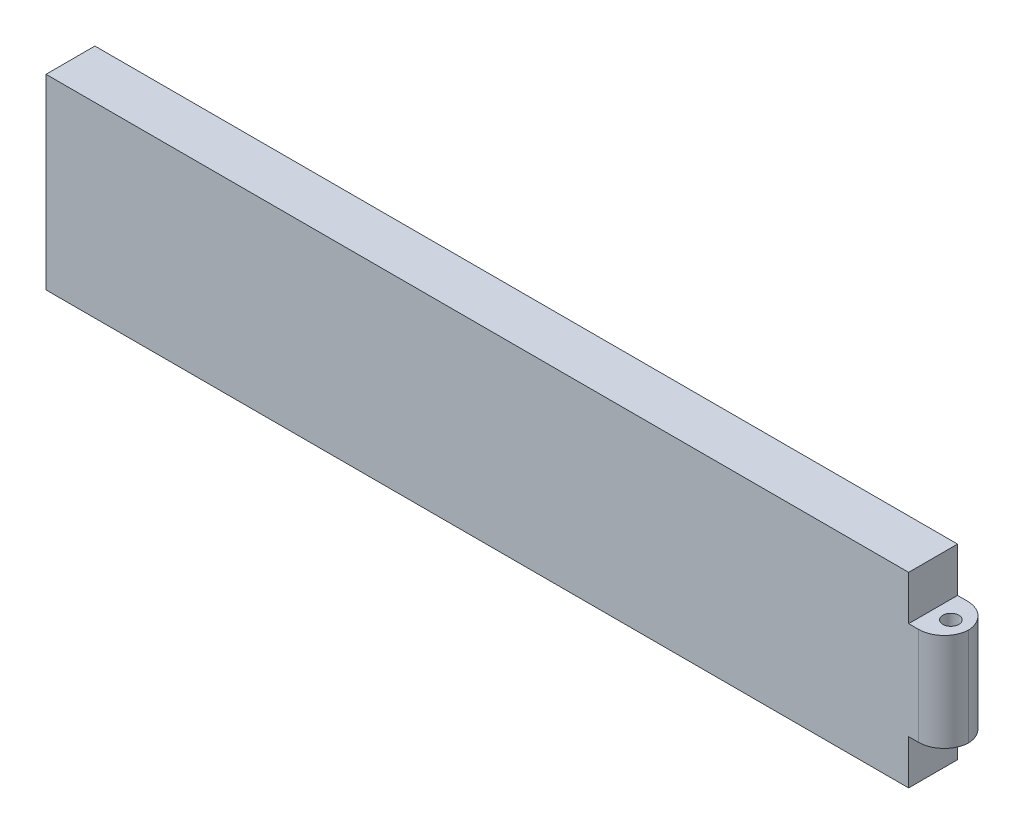
SolidWorks part; units mm, degrees
ref_plane "Front Plane" through (0, 0, 0) normal (0, 0, 1) x (1, 0, 0)
ref_plane "Top Plane" through (0, 0, 0) normal (0, 1, 0) x (1, 0, 0)
ref_plane "Right Plane" through (0, 0, 0) normal (1, 0, 0) x (0, 0, -1)
sketch "Sketch1" plane through (0, 0, 0) normal (0, 1, 0) x (1, 0, 0)
  line L1 (-50.5, -2.75) -> (50.5, -2.75)
  line L2 (-50.5, -2.75) -> (-50.5, 2.75)
  line L3 (-50.5, 2.75) -> (50.5, 2.75)
  line L4 (50.5, -2.75) -> (50.5, 2.75)
  line L5 (-50.5, -2.75) -> (50.5, 2.75) construction
  line L6 (-50.5, 2.75) -> (50.5, -2.75) construction
  point P0 (0, 0)
  dimension "D1" = 101
  dimension "D2" = 5.5
extrude "Boss-Extrude1" add sketch "Sketch1" along normal blind 21
sketch "Sketch2" plane through (0, 0, 0) normal (0, -1, 0) x (1, 0, 0)
  line L0 (-50.5, -2.75) -> (-50.5, 2.75) construction
  line L1 (-49.5, -1.8961) -> (-34.5, -1.8961)
  line L2 (-49.5, -1.8961) -> (-49.5, 1.8961)
  line L3 (-49.5, 1.8961) -> (-34.5, 1.8961)
  line L4 (-34.5, -1.8961) -> (-34.5, 1.8961)
  line L5 (-49.5, -1.8961) -> (-34.5, 1.8961) construction
  line L6 (-49.5, 1.8961) -> (-34.5, -1.8961) construction
  line L7 (-33.5, -1.8961) -> (-18.5, -1.8961)
  line L8 (-33.5, -1.8961) -> (-33.5, 1.8961)
  line L9 (-33.5, 1.8961) -> (-18.5, 1.8961)
  line L10 (-18.5, -1.8961) -> (-18.5, 1.8961)
  line L11 (-33.5, -1.8961) -> (-18.5, 1.8961) construction
  line L12 (-33.5, 1.8961) -> (-18.5, -1.8961) construction
  line L13 (-17.5, -1.8961) -> (-2.5, -1.8961)
  line L14 (-17.5, -1.8961) -> (-17.5, 1.8961)
  line L15 (-17.5, 1.8961) -> (-2.5, 1.8961)
  line L16 (-2.5, -1.8961) -> (-2.5, 1.8961)
  line L17 (-17.5, -1.8961) -> (-2.5, 1.8961) construction
  line L18 (-17.5, 1.8961) -> (-2.5, -1.8961) construction
  line L19 (-1.5, -1.8961) -> (13.5, -1.8961)
  line L20 (-1.5, -1.8961) -> (-1.5, 1.8961)
  line L21 (-1.5, 1.8961) -> (13.5, 1.8961)
  line L22 (13.5, -1.8961) -> (13.5, 1.8961)
  line L23 (-1.5, -1.8961) -> (13.5, 1.8961) construction
  line L24 (-1.5, 1.8961) -> (13.5, -1.8961) construction
  line L25 (14.5, -1.8961) -> (29.5, -1.8961)
  line L26 (14.5, -1.8961) -> (14.5, 1.8961)
  line L27 (14.5, 1.8961) -> (29.5, 1.8961)
  line L28 (29.5, -1.8961) -> (29.5, 1.8961)
  line L29 (14.5, -1.8961) -> (29.5, 1.8961) construction
  line L30 (14.5, 1.8961) -> (29.5, -1.8961) construction
  line L31 (30.5, -1.8961) -> (45.5, -1.8961)
  line L32 (30.5, -1.8961) -> (30.5, 1.8961)
  line L33 (30.5, 1.8961) -> (45.5, 1.8961)
  line L34 (45.5, -1.8961) -> (45.5, 1.8961)
  line L35 (30.5, -1.8961) -> (45.5, 1.8961) construction
  line L36 (30.5, 1.8961) -> (45.5, -1.8961) construction
  line L37 (50.5, 2.75) -> (50.5, -2.75) construction
  circle A0 centre (48.5, 0) radius 0.9
  point P0 (-42, 0)
  point P5 (-26, 0)
  point P10 (-10, 0)
  point P15 (6, 0)
  point P20 (22, 0)
  point P25 (38, 0)
  point P34 (50.5, 0)
  dimension "D13" = 1.8
  dimension "D14" = 2
  dimension "D1" = 1
  dimension "D2" = 15
  dimension "D3" = 1
  dimension "D4" = 1
  dimension "D5" = 1
  dimension "D6" = 1
  dimension "D7" = 1
  dimension "D8" = 15
  dimension "D9" = 15
  dimension "D10" = 15
  dimension "D11" = 15
  dimension "D12" = 15
extrude "Cut-Extrude2" cut sketch "Sketch2" against normal blind 20
sketch "Sketch3" plane through (0, 0, -2.75) normal (0, 0, -1) x (-1, 0, 0)
  line L0 (-50.5, 21) -> (50.5, 21) construction
  line L1 (-46.5, 5) -> (-50.5, 5)
  line L2 (-46.5, 5) -> (-46.5, 0)
  line L3 (-46.5, 0) -> (-50.5, 0)
  line L4 (-50.5, 5) -> (-50.5, 0)
  line L5 (-46.5, 5) -> (-50.5, 0) construction
  line L6 (-46.5, 0) -> (-50.5, 5) construction
  line L7 (-46.5, 16) -> (-50.5, 16)
  line L8 (-46.5, 16) -> (-46.5, 21)
  line L9 (-46.5, 21) -> (-50.5, 21)
  line L10 (-50.5, 16) -> (-50.5, 21)
  line L11 (-46.5, 16) -> (-50.5, 21) construction
  line L12 (-46.5, 21) -> (-50.5, 16) construction
  line L13 (-50.5, 21) -> (-50.5, 0) construction
  point P0 (-48.5, 2.5)
  point P6 (-48.5, 18.5)
  dimension "D1" = 5
  dimension "D2" = 5
  dimension "D3" = 4
  dimension "D4" = 4
extrude "Cut-Extrude3" cut sketch "Sketch3" against normal blind 21
fillet "Fillet1" radius 2.9 2 edges at (50.5, 10.5, 2.75) (50.5, 10.5, -2.75)
sketch "Sketch4" plane through (0, 0, 0) normal (0, -1, 0) x (1, 0, 0)
  line L0 (14.5, -1.8961) -> (29.5, -1.8961) construction
  line L1 (30.5, -1.8961) -> (29.5, -1.8961)
  line L2 (30.5, -1.8961) -> (30.5, 1.8961)
  line L3 (30.5, 1.8961) -> (29.5, 1.8961)
  line L4 (29.5, -1.8961) -> (29.5, 1.8961)
  line L5 (30.5, -1.8961) -> (29.5, 1.8961) construction
  line L6 (30.5, 1.8961) -> (29.5, -1.8961) construction
  line L7 (14.5, -1.8961) -> (13.5, -1.8961)
  line L8 (14.5, -1.8961) -> (14.5, 1.8961)
  line L9 (14.5, 1.8961) -> (13.5, 1.8961)
  line L10 (13.5, -1.8961) -> (13.5, 1.8961)
  line L11 (14.5, -1.8961) -> (13.5, 1.8961) construction
  line L12 (14.5, 1.8961) -> (13.5, -1.8961) construction
  line L13 (-1.5, -1.8961) -> (-2.5, -1.8961)
  line L14 (-1.5, -1.8961) -> (-1.5, 1.8961)
  line L15 (-1.5, 1.8961) -> (-2.5, 1.8961)
  line L16 (-2.5, -1.8961) -> (-2.5, 1.8961)
  line L17 (-1.5, -1.8961) -> (-2.5, 1.8961) construction
  line L18 (-1.5, 1.8961) -> (-2.5, -1.8961) construction
  line L19 (-17.5, 1.8961) -> (-18.5, 1.8961)
  line L20 (-17.5, 1.8961) -> (-17.5, -1.8961)
  line L21 (-17.5, -1.8961) -> (-18.5, -1.8961)
  line L22 (-18.5, 1.8961) -> (-18.5, -1.8961)
  line L23 (-17.5, 1.8961) -> (-18.5, -1.8961) construction
  line L24 (-17.5, -1.8961) -> (-18.5, 1.8961) construction
  line L25 (-33.5, -1.8961) -> (-34.5, -1.8961)
  line L26 (-33.5, -1.8961) -> (-33.5, 1.8961)
  line L27 (-33.5, 1.8961) -> (-34.5, 1.8961)
  line L28 (-34.5, -1.8961) -> (-34.5, 1.8961)
  line L29 (-33.5, -1.8961) -> (-34.5, 1.8961) construction
  line L30 (-33.5, 1.8961) -> (-34.5, -1.8961) construction
  line L31 (29.5, 1.8961) -> (14.5, 1.8961) construction
  line L32 (29.5, -1.8961) -> (29.5, 1.8961) construction
  line L33 (30.5, 1.8961) -> (30.5, -1.8961) construction
  line L34 (-1.5, -1.8961) -> (13.5, -1.8961) construction
  line L35 (13.5, 1.8961) -> (-1.5, 1.8961) construction
  line L36 (13.5, -1.8961) -> (13.5, 1.8961) construction
  line L37 (14.5, 1.8961) -> (14.5, -1.8961) construction
  line L38 (-2.5, -1.8961) -> (-2.5, 1.8961) construction
  line L39 (-1.5, 1.8961) -> (-1.5, -1.8961) construction
  line L40 (-2.5, 1.8961) -> (-17.5, 1.8961) construction
  line L41 (-17.5, -1.8961) -> (-2.5, -1.8961) construction
  line L42 (-18.5, -1.8961) -> (-18.5, 1.8961) construction
  line L43 (-17.5, 1.8961) -> (-17.5, -1.8961) construction
  line L44 (-33.5, -1.8961) -> (-18.5, -1.8961) construction
  line L45 (-18.5, 1.8961) -> (-33.5, 1.8961) construction
  line L46 (-34.5, -1.8961) -> (-34.5, 1.8961) construction
  line L48 (-33.5, 1.8961) -> (-33.5, -1.8961) construction
  point P0 (30, 0)
  point P5 (14, 0)
  point P10 (-2, 0)
  point P15 (-18, 0)
  point P20 (-34, 0)
  dimension "D1" = 0
  dimension "D2" = 0
  dimension "D3" = 0
  dimension "D4" = 0
  dimension "D5" = 0
  dimension "D6" = 0
  dimension "D7" = 0
  dimension "D8" = 0
  dimension "D9" = 0
  dimension "D10" = 0
  dimension "D11" = 0
  dimension "D12" = 0
  dimension "D13" = 0
  dimension "D14" = 0
  dimension "D15" = 0
  dimension "D16" = 0
  dimension "D17" = 0
  dimension "D18" = 0
  dimension "D19" = 0
  dimension "D20" = 0
extrude "Cut-Extrude4" cut sketch "Sketch4" against normal blind 1
sketch "Sketch7" plane through (0, 0, -2.75) normal (0, 0, -1) x (-1, 0, 0)
  line L0 (0, 0) -> (0, 20.6478) construction
  line L1 (0, 10.3239) -> (-49.6862, 10.3239) construction
  line L2 (0, 10.3239) -> (50.9901, 10.3239) construction
  line L3 (50.5, 21) -> (50.5, 0) construction
  circle A0 centre (44.325, 10.3239) radius 3
  circle A1 centre (44.325, 10.3239) radius 4
  circle A2 centre (31.625, 10.3239) radius 3
  circle A3 centre (31.625, 10.3239) radius 4
  circle A4 centre (18.925, 10.3239) radius 3
  circle A5 centre (18.925, 10.3239) radius 4
  circle A6 centre (6.225, 10.3239) radius 3
  circle A7 centre (6.225, 10.3239) radius 4
  circle A8 centre (-6.475, 10.3239) radius 3
  circle A9 centre (-6.475, 10.3239) radius 4
  circle A10 centre (-19.175, 10.3239) radius 3
  circle A11 centre (-19.175, 10.3239) radius 4
  dimension "D1" = 6
  dimension "D2" = 6.175
  dimension "D3" = 8
  dimension "D4" = 12.7
  dimension "D5" = 12.7
  dimension "D6" = 12.7
  dimension "D7" = 12.7
  dimension "D8" = 12.7
extrude "Boss-Extrude2" add sketch "Sketch7" along normal blind 3.175
fillet "Fillet2" radius 2 6 edges at (15.175, 10.3239, -5.925) (2.475, 10.3239, -5.925) (-48.325, 10.3239, -5.925) (-35.625, 10.3239, -5.925) (-22.925, 10.3239, -5.925) (-10.225, 10.3239, -5.925)
